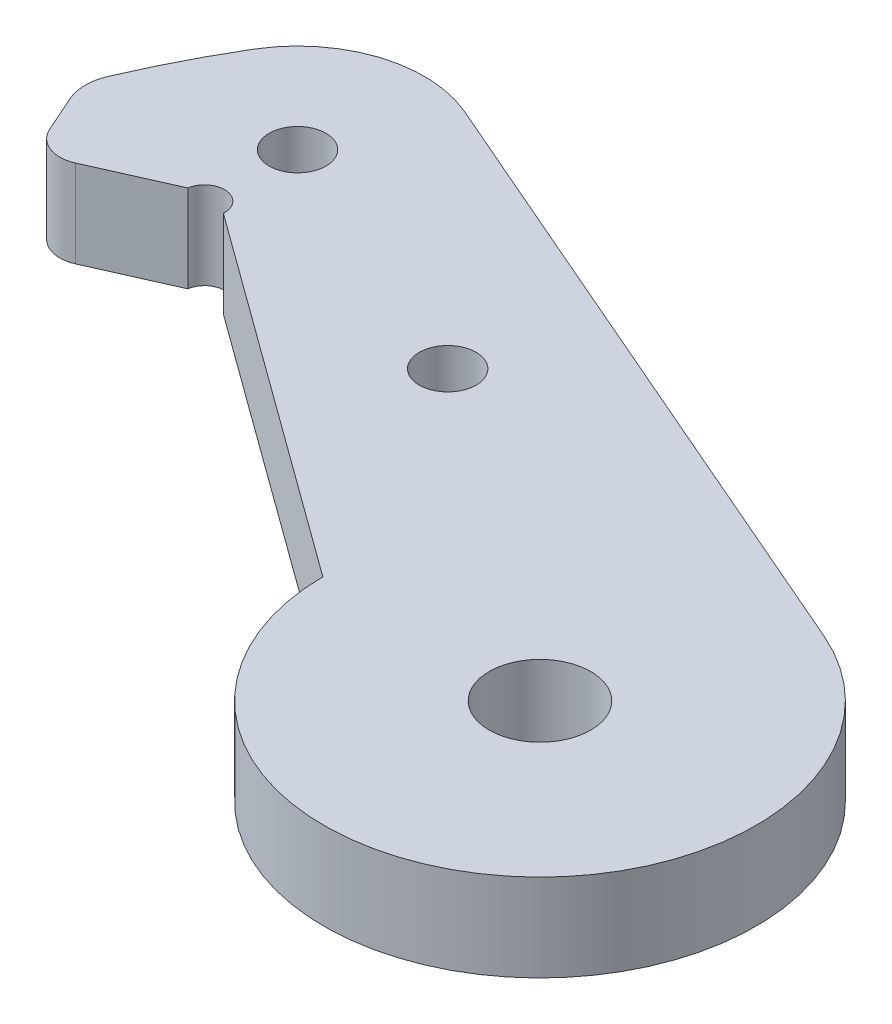
SolidWorks part; units mm, degrees
ref_plane "Front" through (0, 0, 0) normal (0, 0, 1) x (1, 0, 0)
ref_plane "Top" through (0, 0, 0) normal (0, 1, 0) x (1, 0, 0)
ref_plane "Right" through (0, 0, 0) normal (1, 0, 0) x (0, 0, -1)
ref_axis "side-side" through (80.9, 0, 0) along (-1, 0, 0)
ref_axis "up-down" through (0, 50, 0) along (0, -1, 0)
ref_axis "front-back" through (0, 0, -80.9) along (0, 0, 1)
sketch "Sketch1" plane through (0, 0, 0) normal (0, 1, 0) x (1, 0, 0)
  line L0 (-37.5348, 16.5677) -> (-37.4529, 17.3438) construction
  line L1 (-38.7702, 16.758) -> (-43.6254, 14.5987)
  line L2 (-36.2869, 16.4959) -> (-13.4998, -0.0747)
  line L3 (-46.2656, 15.6135) -> (-47.2827, 17.9005)
  line L4 (-34.2596, 29.5434) -> (5.3636, 12.3888) construction
  line L5 (-34.2596, 29.5434) -> (5.3636, 12.3888)
  line L6 (-36.2869, 16.4959) -> (-38.7702, 16.758) construction
  arc A0 (-43.6254, 14.5987) -> (-46.2656, 15.6135) centre (-44.4381, 16.4262) cw
  arc A1 (-47.2983, 20.3029) -> (-44.2347, 26.3178) centre (0, 0) cw
  arc A2 (-47.2983, 20.3029) -> (-47.2827, 17.9005) centre (-44.5415, 19.1196) ccw
  arc A3 (-34.2596, 29.5434) -> (-44.2347, 26.3178) centre (-37.4133, 22.2593) ccw
  arc A4 (-38.7702, 16.758) -> (-36.2869, 16.4959) centre (-37.5348, 16.5677) cw
  arc A5 (-13.4998, -0.0747) -> (5.3636, 12.3888) centre (0, 0) ccw
  circle A10 centre (8, 0) radius 1.75 construction
  circle A11 centre (0, -8) radius 1.75 construction
  circle A12 centre (-8, 0) radius 1.75 construction
  circle A13 centre (0, 8) radius 1.75 construction
  circle A14 centre (-20.8625, 15.0937) radius 1.778
  circle A15 centre (0, 0) radius 3.175
  circle A16 centre (-20.8625, 15.0937) radius 7.9375 construction
  arc A17 (-34.2596, 29.5434) -> (-44.2347, 26.3178) centre (-37.4133, 22.2593) ccw construction
  circle A18 centre (-37.4133, 22.2593) radius 1.778
  point P0 (-37.4529, 17.3438)
  point P11 (-45.4529, 13.786)
  dimension "D2" = 3
  dimension "D8" = 2
  dimension "D9" = 0.7804
  dimension "D7" = 1.25
  dimension "D11" = 15.875
  dimension "D13" = 6.35
  dimension "D14" = 3.556
  dimension "D1" = 8.7554
  dimension "D3" = 8
  dimension "D6" = 120
  dimension "D12" = 25.75
extrude "Boss-Extrude1" add sketch "Sketch1" along normal blind 5.461
